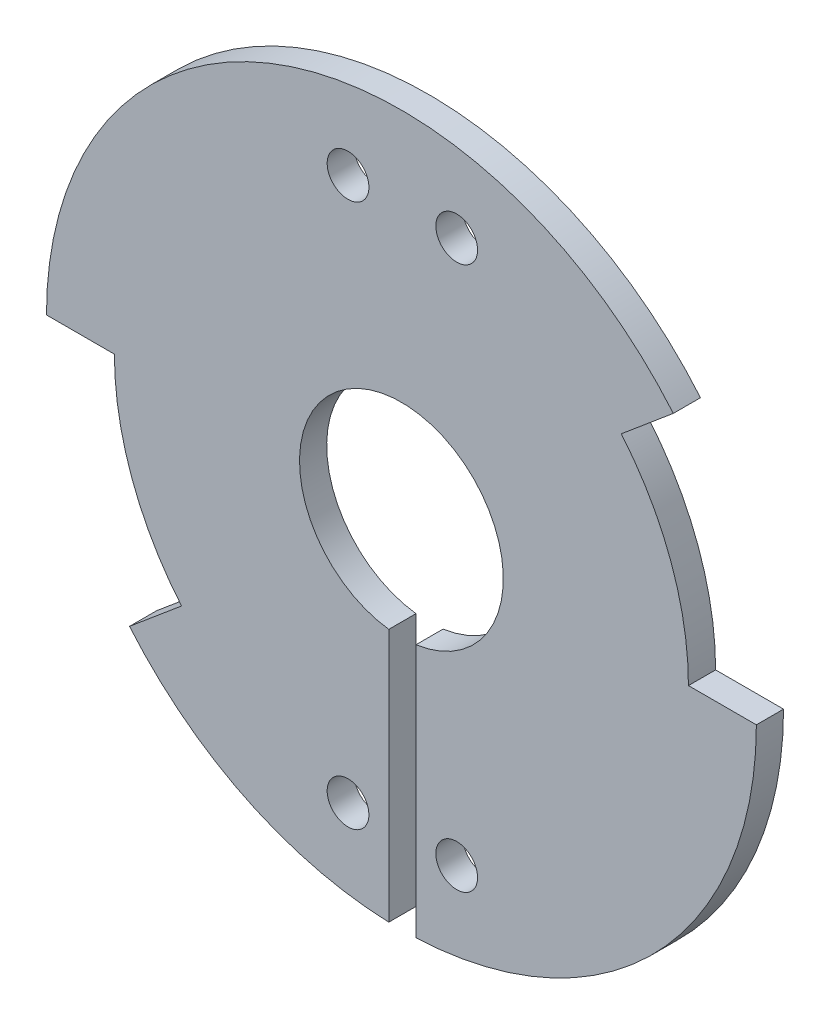
SolidWorks part; units mm, degrees
ref_plane "Front Plane" through (0, 0, 0) normal (0, 0, 1) x (1, 0, 0)
ref_plane "Top Plane" through (0, 0, 0) normal (0, 1, 0) x (1, 0, 0)
ref_plane "Right Plane" through (0, 0, 0) normal (1, 0, 0) x (0, 0, -1)
sketch "Sketch1" plane through (0, 0, 0) normal (0, 0, 1) x (1, 0, 0)
  circle A0 centre (0, 0) radius 66.3575
extrude "Boss-Extrude1" add sketch "Sketch1" along normal blind 5.08
sketch "Sketch3" plane through (0, 0, 0) normal (0, 0, 1) x (1, 0, 0)
  line L0 (0, 0) -> (66.3575, 0) construction
  line L1 (2.7181, -67.8586) -> (-2.3619, -67.8586)
  line L2 (2.7181, -67.8586) -> (2.7181, -8.6651)
  line L3 (2.7181, -8.6651) -> (-2.3619, -8.6651)
  line L4 (-2.3619, -67.8586) -> (-2.3619, -8.6651)
  line L5 (2.7181, -67.8586) -> (-2.3619, -8.6651) construction
  line L6 (2.7181, -8.6651) -> (-2.3619, -67.8586) construction
  line L7 (66.3575, 0) -> (-66.3575, 0) construction
  line L8 (-53.6575, 0) -> (-66.3575, 0)
  line L9 (-41.104, -34.4904) -> (-50.8328, -42.6538)
  line L10 (41.104, 34.4904) -> (50.8328, 42.6538)
  line L11 (53.6575, 0) -> (66.3575, 0)
  circle A0 centre (0, 0) radius 19.05
  circle A2 centre (-9.9819, -50.8) radius 3.9006
  circle A3 centre (10.3381, -50.8) radius 3.9006
  circle A4 centre (0, 0) radius 66.3575 construction
  circle A5 centre (10.3381, 50.8) radius 3.9006
  circle A6 centre (-9.9819, 50.8) radius 3.9006
  arc A8 (-41.104, -34.4904) -> (-53.6575, 0) centre (0, 0) cw
  circle A9 centre (0, 0) radius 53.6575
  circle A10 centre (0, 0) radius 53.6575 construction
  arc A11 (41.104, 34.4904) -> (53.6575, 0) centre (0, 0) cw
  arc A12 (-66.3575, 0) -> (-50.7671, -42.732) centre (0, 0) ccw
  arc A13 (50.8328, 42.6538) -> (66.3575, 0) centre (0, 0) cw
  point P3 (0.1781, -38.2619)
  point P31 (0, 0)
  dimension "D1" = 5.08
  dimension "D4" = 50.8
  dimension "D2" = 7.62
  dimension "D3" = 7.62
  dimension "D5" = 50.8
  dimension "D7" = 2
  dimension "D6" = 12.7
extrude "Cut-Extrude1" cut sketch "Sketch3" along normal up to next contours A0
extrude "Cut-Extrude2" cut sketch "Sketch3<4>" along normal up to next contours L8 A12 L9 A8 | A13 L10 A11 L11 | A3 | A2 | A5 | A6 | L2 L3 L4 L1 region at (55.4567, 20.1846, 0) region at (-55.4567, -20.1846, 0)
sketch "Sketch3<4>" plane through (0, 0, 0) normal (0, 0, 1) x (1, 0, 0) same geometry as "Sketch3"
